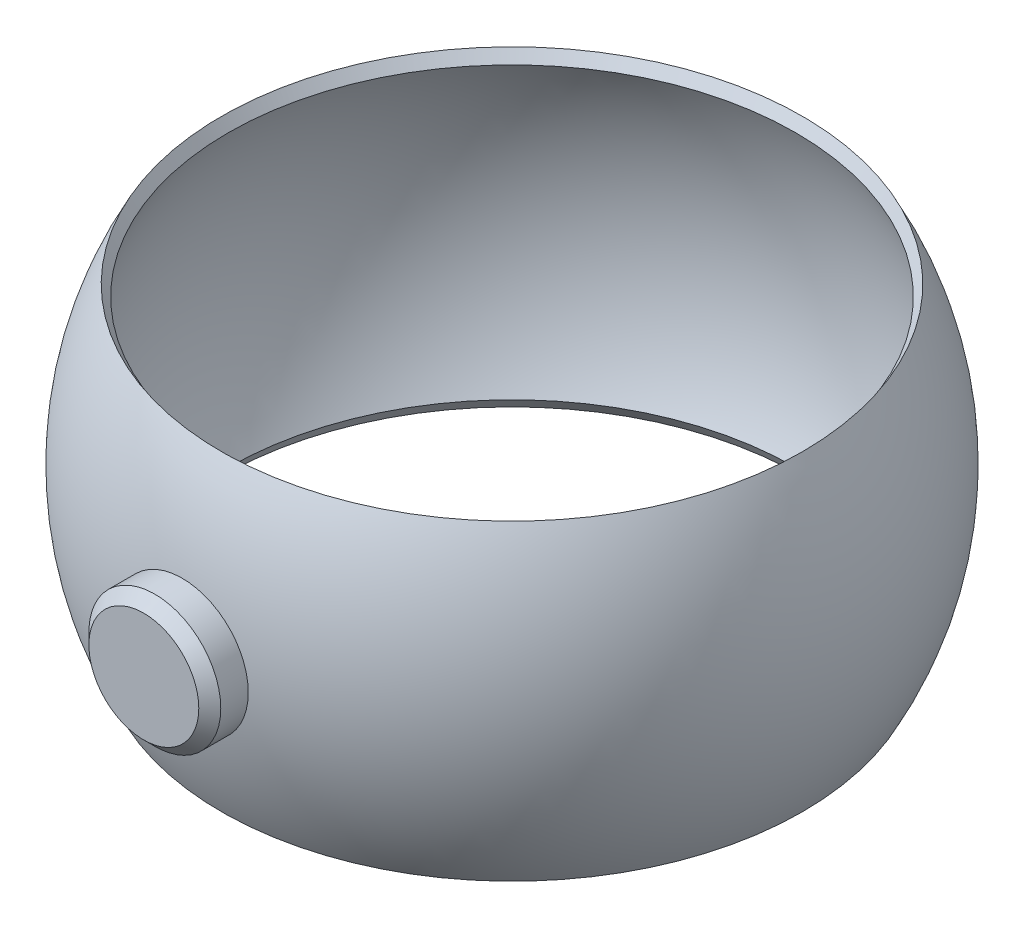
SolidWorks part; units mm, degrees
ref_plane "Front Plane" through (0, 0, 0) normal (0, 0, 1) x (1, 0, 0)
ref_plane "Top Plane" through (0, 0, 0) normal (0, 1, 0) x (1, 0, 0)
ref_plane "Right Plane" through (0, 0, 0) normal (1, 0, 0) x (0, 0, -1)
sketch "Sketch2" plane through (0, 0, 0) normal (0, 0, 1) x (1, 0, 0)
  line L0 (0, 7.5) -> (0, -7.5)
  line L1 (0, 7.5) -> (12.9904, 7.5)
  line L2 (0, -7.5) -> (12.9904, -7.5)
  arc A0 (12.9904, 7.5) -> (12.9904, -7.5) centre (0, 0) cw
  point P3 (0, 0)
  point P4 (0, 0)
  point P8 (0, 0)
  point P9 (0, 0)
  point P10 (4.4204, -1.34)
  dimension "D1" = 15
  dimension "D3" = 15
revolve "Revolve1" add sketch "Sketch2" angle 360 about L0
shell "Shell2" thickness 0.5
chamfer "Chamfer4" distance 1.1 2 edges at (-12.4097, 7.5, 0) (-12.4097, -7.5, 0)
ref_plane "Plane1" through (0, 0, 15) normal (0, 0, 1) x (1, 0, 0)
sketch "Sketch4" plane through (0, 0, 15) normal (0, 0, 1) x (1, 0, 0)
  circle A0 centre (0, 0) radius 3
  dimension "D1" = 6
extrude "Boss-Extrude1" add sketch "Sketch4" along normal blind 1.75 separate body
chamfer "Chamfer5" distance 0.5 angle 45 1 edges at (3, 0, 16.75)
